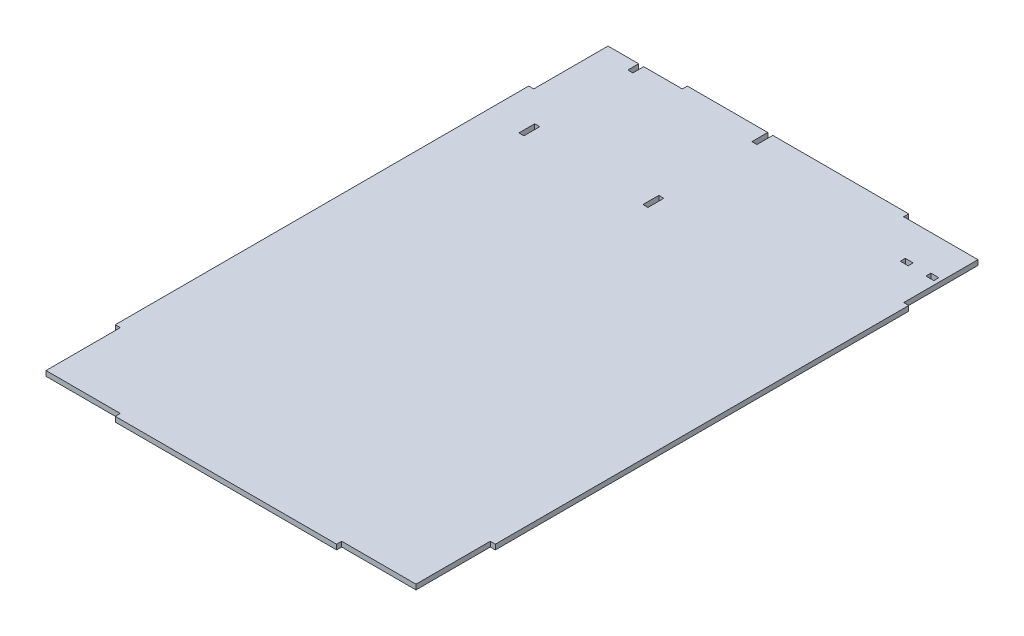
SolidWorks part; units mm, degrees
ref_plane "Front Plane" through (0, 0, 0) normal (0, 0, 1) x (1, 0, 0)
ref_plane "Top Plane" through (0, 0, 0) normal (0, 1, 0) x (1, 0, 0)
ref_plane "Right Plane" through (0, 0, 0) normal (1, 0, 0) x (0, 0, -1)
sketch "Sketch1" plane through (0, 0, 0) normal (0, 1, 0) x (1, 0, 0)
  line L7 (-239.5, -360.5) -> (239.5, -360.5)
  line L8 (-239.5, -360.5) -> (-239.5, 360.5)
  line L9 (-239.5, 360.5) -> (239.5, 360.5)
  line L10 (239.5, -360.5) -> (239.5, 360.5)
  point P0 (0, 0)
  point P3 (239.5, 0)
  point P6 (0, 0)
  point P11 (0, -360.5)
  dimension "D1" = 721
  dimension "D2" = 479
extrude "Boss-Extrude1" add sketch "Sketch1" along normal mid plane 6.35
sketch "Sketch2" plane through (0, 3.175, 0) normal (0, 1, 0) x (1, 0, 0)
  line L0 (-239.5, 360.5) -> (-239.5, 260.5)
  line L1 (-239.5, 360.5) -> (-239.5, -360.5) construction
  line L2 (-239.5, 260.5) -> (-233.15, 260.5)
  line L3 (-233.15, 260.5) -> (-233.15, 354.15)
  line L4 (-233.15, 354.15) -> (-139.5, 354.15)
  line L5 (-139.5, 354.15) -> (-139.5, 360.5)
  line L6 (239.5, 360.5) -> (-239.5, 360.5) construction
  line L7 (-139.5, 360.5) -> (-239.5, 360.5)
  line L8 (239.5, 360.5) -> (139.5, 360.5)
  line L9 (139.5, 360.5) -> (139.5, 354.15)
  line L10 (139.5, 354.15) -> (233.15, 354.15)
  line L11 (233.15, 354.15) -> (233.15, 260.5)
  line L12 (233.15, 260.5) -> (239.5, 260.5)
  line L13 (239.5, -360.5) -> (239.5, 360.5) construction
  line L14 (239.5, 260.5) -> (239.5, 360.5)
  line L15 (239.5, -360.5) -> (239.5, -260.5)
  line L16 (239.5, -260.5) -> (233.15, -260.5)
  line L17 (233.15, -260.5) -> (233.15, -354.15)
  line L18 (233.15, -354.15) -> (139.5, -354.15)
  line L19 (139.5, -354.15) -> (139.5, -360.5)
  line L20 (-239.5, -360.5) -> (239.5, -360.5) construction
  line L21 (139.5, -360.5) -> (239.5, -360.5)
  line L22 (-239.5, -360.5) -> (-139.5, -360.5)
  line L23 (-139.5, -360.5) -> (-139.5, -354.15)
  line L24 (-139.5, -354.15) -> (-233.15, -354.15)
  line L25 (-233.15, -354.15) -> (-233.15, -260.5)
  line L26 (-233.15, -260.5) -> (-239.5, -260.5)
  line L27 (-239.5, -260.5) -> (-239.5, -360.5)
  dimension "D1" = 100
  dimension "D2" = 6.35
extrude "Cut-Extrude1" cut sketch "Sketch2" against normal through all
sketch "Sketch3" plane through (0, -3.175, 0) normal (0, -1, 0) x (1, 0, 0)
  line L0 (233.15, -354.15) -> (233.15, -260.5) construction
  line L1 (139.5, -354.15) -> (233.15, -354.15) construction
  line L2 (139.5, -360.5) -> (-139.5, -360.5) construction
  line L3 (-31.8, -360.5) -> (-38.15, -360.5)
  line L4 (-31.8, -360.5) -> (-31.8, -340.5)
  line L5 (-31.8, -340.5) -> (-38.15, -340.5)
  line L6 (-38.15, -360.5) -> (-38.15, -340.5)
  line L7 (-233.15, -260.5) -> (-233.15, -354.15) construction
  line L8 (185.85, -303.45) -> (195.85, -303.45)
  line L9 (185.85, -303.45) -> (185.85, -309.8)
  line L10 (185.85, -309.8) -> (195.85, -309.8)
  line L11 (195.85, -303.45) -> (195.85, -309.8)
  line L12 (228.15, -303.45) -> (228.15, -309.8)
  line L13 (218.15, -303.45) -> (228.15, -303.45)
  line L14 (218.15, -303.45) -> (218.15, -309.8)
  line L15 (218.15, -309.8) -> (228.15, -309.8)
  line L16 (-188.15, -360.5) -> (-194.5, -360.5)
  line L17 (-188.15, -360.5) -> (-188.15, -340.5)
  line L18 (-188.15, -340.5) -> (-194.5, -340.5)
  line L19 (-194.5, -360.5) -> (-194.5, -340.5)
  line L20 (-31.8, -223.15) -> (-38.15, -223.15)
  line L21 (-31.8, -223.15) -> (-31.8, -203.15)
  line L22 (-31.8, -203.15) -> (-38.15, -203.15)
  line L23 (-38.15, -223.15) -> (-38.15, -203.15)
  line L24 (-188.15, -223.15) -> (-194.5, -223.15)
  line L25 (-188.15, -223.15) -> (-188.15, -203.15)
  line L26 (-188.15, -203.15) -> (-194.5, -203.15)
  line L27 (-194.5, -223.15) -> (-194.5, -203.15)
  dimension "D1" = 10
  dimension "D2" = 6.35
  dimension "D3" = 5
  dimension "D4" = 42.3
  dimension "D5" = 44.35
  dimension "D6" = 6.35
  dimension "D7" = 20
  dimension "D8" = 117.35
  dimension "D9" = 150
  dimension "D10" = 45
extrude "Cut-Extrude2" cut sketch "Sketch3" against normal through all
